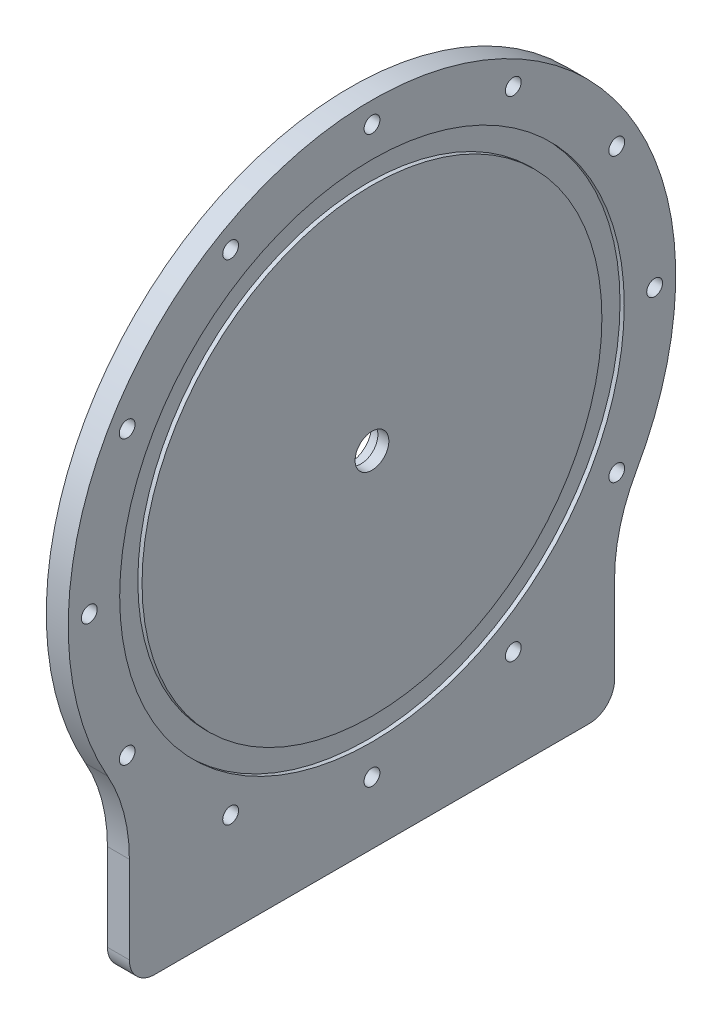
SolidWorks part; units mm, degrees
material "6061 Alloy"
ref_plane "Front Plane" through (0, 0, 0) normal (0, 0, 1) x (1, 0, 0)
ref_plane "Top Plane" through (0, 0, 0) normal (0, 1, 0) x (1, 0, 0)
ref_plane "Right Plane" through (0, 0, 0) normal (1, 0, 0) x (0, 0, -1)
sketch "Sketch1" plane through (0, 0, 0) normal (1, 0, 0) x (0, 0, -1)
  line L0 (0, -1000) -> (0, 49000) construction
  line L1 (5.5562, 0) -> (2.7781, 4.8119) construction
  line L2 (2.7781, 4.8119) -> (-2.7781, 4.8119) construction
  line L3 (-2.7781, 4.8119) -> (-5.5562, 0) construction
  line L4 (-5.5562, 0) -> (-2.7781, -4.8119) construction
  line L5 (-2.7781, -4.8119) -> (2.7781, -4.8119) construction
  line L6 (2.7781, -4.8119) -> (5.5562, 0) construction
  line L7 (-65.405, -103.8551) -> (65.405, -103.8551)
  line L8 (-73.025, -96.2351) -> (-73.025, -69.997)
  line L10 (73.025, -96.2351) -> (73.025, -69.997)
  circle A0 centre (0, 0) radius 69.85 construction
  circle A1 centre (0, 0) radius 76.2 construction
  circle A2 centre (0, 0) radius 5.08
  circle A3 centre (0, 0) radius 3.9688 construction
  arc A4 (79.6018, -44.9981) -> (-79.6018, -44.9981) centre (0, 0) ccw
  circle A5 centre (0, 0) radius 11.5094 construction
  circle A6 centre (0, 0) radius 91.44 construction
  arc A7 (65.405, -103.8551) -> (73.025, -96.2351) centre (65.405, -96.2351) ccw
  arc A8 (-65.405, -103.8551) -> (-73.025, -96.2351) centre (-65.405, -96.2351) cw
  arc A9 (79.6018, -44.9981) -> (73.025, -69.997) centre (123.825, -69.997) ccw
  arc A10 (-73.025, -69.997) -> (-79.6018, -44.9981) centre (-123.825, -69.997) ccw
  point P19 (73.025, -103.8551)
  point P26 (-73.025, -103.8551)
  dimension "D1" = 152.4
  dimension "D2" = 139.7
  dimension "D3" = 10.16
  dimension "D4" = 7.9375
  dimension "D5" = 15.24
  dimension "D6" = 23.0188
  dimension "D8" = 7.62
  dimension "D9" = 50.8
  dimension "D7" = 146.05
extrude "Boss-Extrude1" add sketch "Sketch1" along normal blind 6.604
sketch "Sketch2" plane through (0, 0, 0) normal (1, 0, 0) x (0, 0, -1)
  circle A0 centre (0, 0) radius 6.35 construction
  circle A1 centre (0, 0) radius 6.477
  dimension "D1" = 12.7
  dimension "D2" = 12.954
extrude "Cut-Extrude1" cut sketch "Sketch2" along direction (1, 0, 0) on the side of the normal blind 3.302
sketch "Sketch3" plane through (6.604, 0, 0) normal (1, 0, 0) x (0, 0, -1)
  circle A0 centre (0, 0) radius 75.946
  circle A1 centre (0, 0) radius 69.215
  dimension "D2" = 138.43
  dimension "D1" = 6.731
extrude "Cut-Extrude2" cut sketch "Sketch3" against normal blind 1.27
sketch "Sketch4" plane through (0, 0, 0) normal (-1, 0, 0) x (0, 0, 1)
  line L0 (0, -1000) -> (0, 49000) construction
  line L1 (-1000, 0) -> (49000, 0) construction
  circle A1 centre (0, 85.09) radius 2.3812
  circle A3 centre (0, 0) radius 85.09 construction
  circle A4 centre (42.545, 73.6901) radius 2.3812
  circle A5 centre (73.6901, 42.545) radius 2.3813
  circle A6 centre (85.09, 0) radius 2.3813
  circle A7 centre (73.6901, -42.545) radius 2.3813
  circle A8 centre (42.545, -73.6901) radius 2.3812
  circle A9 centre (0, -85.09) radius 2.3812
  circle A10 centre (-42.545, -73.6901) radius 2.3812
  circle A11 centre (-73.6901, -42.545) radius 2.3813
  circle A12 centre (-85.09, 0) radius 2.3813
  circle A13 centre (-73.6901, 42.545) radius 2.3813
  circle A14 centre (-42.545, 73.6901) radius 2.3812
  point P34 (0, 0)
  dimension "D2" = 12
extrude "Cut-Extrude3" cut sketch "Sketch4" against normal through all
sketch "Sketch5" plane through (0, 0, 0) normal (-1, 0, 0) x (0, 0, 1)
  circle A0 centre (0, 85.09) radius 3.7783
  circle A3 centre (42.545, 73.6901) radius 3.7783
  circle A5 centre (-42.545, 73.6901) radius 3.7783
  circle A6 centre (73.6901, 42.545) radius 3.7783
  circle A7 centre (85.09, 0) radius 3.7783
  circle A8 centre (73.6901, -42.545) radius 3.7783
  circle A9 centre (42.545, -73.6901) radius 3.7783
  circle A10 centre (0, -85.09) radius 3.7783
  circle A11 centre (-42.545, -73.6901) radius 3.7783
  circle A12 centre (-73.6901, -42.545) radius 3.7783
  circle A13 centre (-85.09, 0) radius 3.7783
  circle A14 centre (-73.6901, 42.545) radius 3.7783
  point P29 (0, 0)
  dimension "D1" = 12
extrude "Cut-Extrude4" cut sketch "Sketch5" against normal blind 1.27
